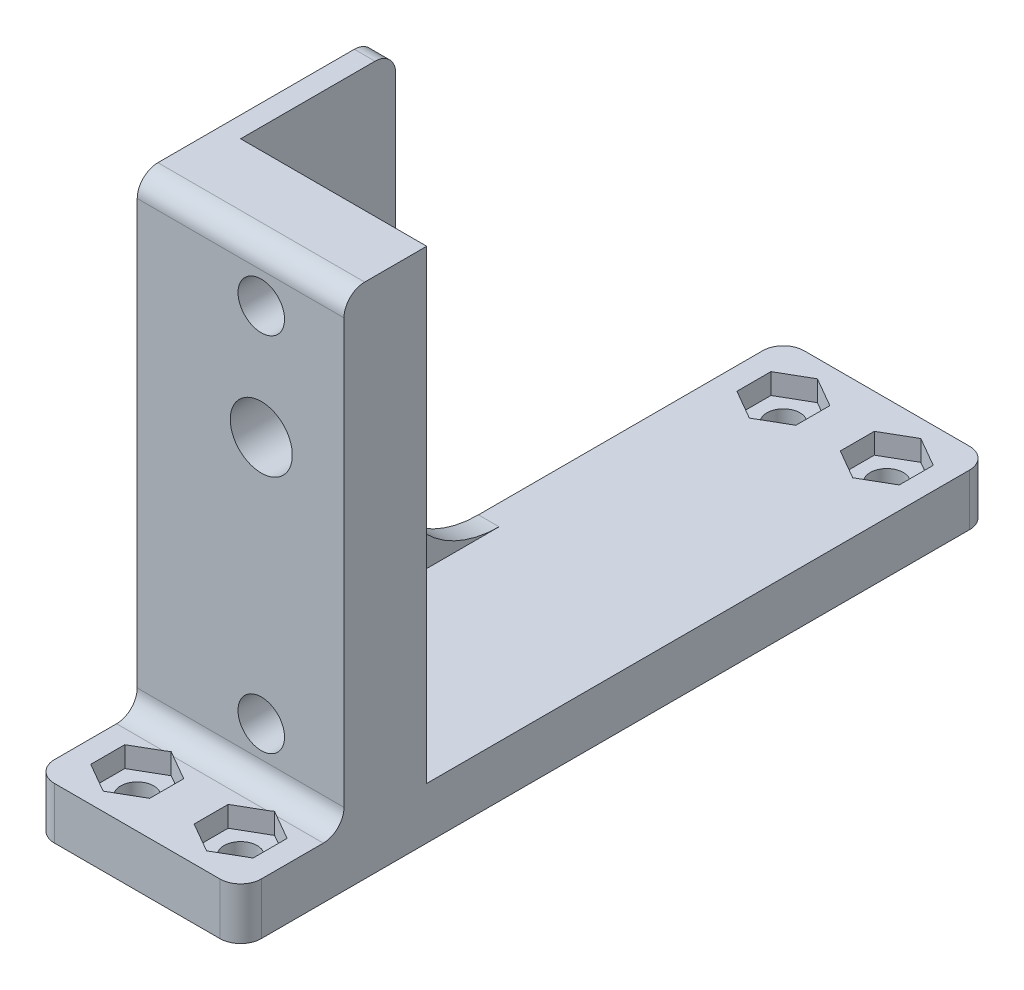
SolidWorks part; units mm, degrees
ref_plane "Alzado" through (0, 0, 0) normal (0, 0, 1) x (1, 0, 0)
ref_plane "Planta" through (0, 0, 0) normal (0, 1, 0) x (1, 0, 0)
ref_plane "Vista lateral" through (0, 0, 0) normal (1, 0, 0) x (0, 0, -1)
sketch "Croquis1" plane through (0, 0, 0) normal (0, 1, 0) x (1, 0, 0)
  line L1 (5, -31.25) -> (-5, -31.25) construction
  line L2 (5, -31.25) -> (5, 31.25) construction
  line L3 (5, 31.25) -> (-5, 31.25) construction
  line L4 (-5, -31.25) -> (-5, 31.25) construction
  line L5 (5, -31.25) -> (-5, 31.25) construction
  line L6 (5, 31.25) -> (-5, -31.25) construction
  line L7 (-10, 36.25) -> (10, 36.25)
  line L8 (-10, 36.25) -> (-10, -36.25)
  line L9 (-10, -36.25) -> (10, -36.25)
  line L10 (10, 36.25) -> (10, -36.25)
  circle A0 centre (-5, 31.25) radius 1.6
  circle A1 centre (5, 31.25) radius 1.6
  circle A2 centre (-5, -31.25) radius 1.6
  circle A3 centre (5, -31.25) radius 1.6
  point P0 (0, 0)
  point P14 (-10, 0)
  point P15 (0, -36.25)
  dimension "D3" = 3.2
  dimension "D1" = 10
  dimension "D2" = 62.5
  dimension "D4" = 20
  dimension "D5" = 72.5
extrude "Saliente-Extruir1" add sketch "Croquis1" along normal blind 5
sketch "Croquis2" plane through (0, 5, 0) normal (0, 1, 0) x (1, 0, 0)
  line L1 (-2.15, 29.6046) -> (-2.15, 32.8954)
  line L2 (-2.15, 32.8954) -> (-5, 34.5409)
  line L3 (-5, 34.5409) -> (-7.85, 32.8954)
  line L4 (-7.85, 32.8954) -> (-7.85, 29.6046)
  line L5 (-7.85, 29.6046) -> (-5, 27.9591)
  line L6 (-5, 27.9591) -> (-2.15, 29.6046)
  line L7 (5, 27.9591) -> (7.85, 29.6046)
  line L8 (7.85, 29.6046) -> (7.85, 32.8954)
  line L9 (7.85, 32.8954) -> (5, 34.5409)
  line L10 (5, 34.5409) -> (2.15, 32.8954)
  line L11 (2.15, 32.8954) -> (2.15, 29.6046)
  line L12 (2.15, 29.6046) -> (5, 27.9591)
  line L13 (-5, -34.5409) -> (-2.15, -32.8954)
  line L14 (-2.15, -32.8954) -> (-2.15, -29.6046)
  line L15 (-2.15, -29.6046) -> (-5, -27.9591)
  line L16 (-5, -27.9591) -> (-7.85, -29.6046)
  line L17 (-7.85, -29.6046) -> (-7.85, -32.8954)
  line L18 (-7.85, -32.8954) -> (-5, -34.5409)
  line L19 (5, -27.9591) -> (2.15, -29.6046)
  line L20 (2.15, -29.6046) -> (2.15, -32.8954)
  line L21 (2.15, -32.8954) -> (5, -34.5409)
  line L22 (5, -34.5409) -> (7.85, -32.8954)
  line L23 (7.85, -32.8954) -> (7.85, -29.6046)
  line L24 (7.85, -29.6046) -> (5, -27.9591)
  circle A0 centre (-5, 31.25) radius 2.85 construction
  circle A1 centre (5, 31.25) radius 2.85 construction
  circle A2 centre (-5, -31.25) radius 2.85 construction
  circle A3 centre (5, -31.25) radius 2.85 construction
  dimension "D1" = 5.7
extrude "Cortar-Extruir1" cut sketch "Croquis2" against normal blind 2
sketch "Croquis3" plane through (0, 5, 0) normal (0, 1, 0) x (1, 0, 0)
  line L1 (-10, -26.25) -> (10, -26.25)
  line L2 (-10, -26.25) -> (-10, -18.25)
  line L3 (-10, -18.25) -> (10, -18.25)
  line L4 (10, -26.25) -> (10, -18.25)
  line L5 (10, -36.25) -> (10, 36.25) construction
  line L6 (-10, -36.25) -> (10, -36.25) construction
  line L7 (-10, 36.25) -> (-10, -36.25) construction
  dimension "D1" = 8
  dimension "D2" = 10
extrude "Saliente-Extruir2" add sketch "Croquis3" along normal blind 45
sketch "Croquis4" plane through (0, 0, 18.25) normal (0, 0, -1) x (-1, 0, 0)
  line L0 (-10, 5) -> (10, 5) construction
  line L1 (10, 50) -> (10, 5) construction
  circle A0 centre (-2, 10) radius 2.25
  circle A1 centre (-2, 45) radius 2.25
  circle A2 centre (-2, 34) radius 3
  dimension "D1" = 35
  dimension "D2" = 4.5
  dimension "D3" = 5
  dimension "D4" = 6
  dimension "D6" = 12
  dimension "D5" = 11
extrude "Cortar-Extruir2" cut sketch "Croquis4" against normal blind 45
sketch "Croquis5" plane through (-10, 0, 0) normal (-1, 0, 0) x (0, 0, 1)
  line L0 (18.25, 5) -> (18.25, 50)
  line L1 (18.25, 50) -> (3.25, 50)
  line L2 (3.25, 5) -> (18.25, 5)
  line L3 (18.25, 50) -> (18.25, 5) construction
  line L4 (3.25, 50) -> (3.25, 5)
  line L5 (-36.25, 5) -> (18.25, 5) construction
  line L6 (18.25, 50) -> (26.25, 50) construction
  circle A0 centre (13.15, 42) radius 1.6
  circle A1 centre (13.15, 10) radius 1.6
  dimension "D2" = 32
  dimension "D3" = 3.2
  dimension "D4" = 8
  dimension "D5" = 5.1
  dimension "D1" = 15
extrude "Saliente-Extruir3" add sketch "Croquis5" against normal blind 2
fillet "Redondeo2" radius 2 7 edges at (10, 2.5, 36.25) (-10, 2.5, 36.25) (10, 2.5, -36.25) (-10, 2.5, -36.25) (-9, 50, 3.25) (0, 50, 26.25) (0, 5, 26.25)
fillet "Redondeo3" radius 10 1 edges at (-9, 5, 3.25)
